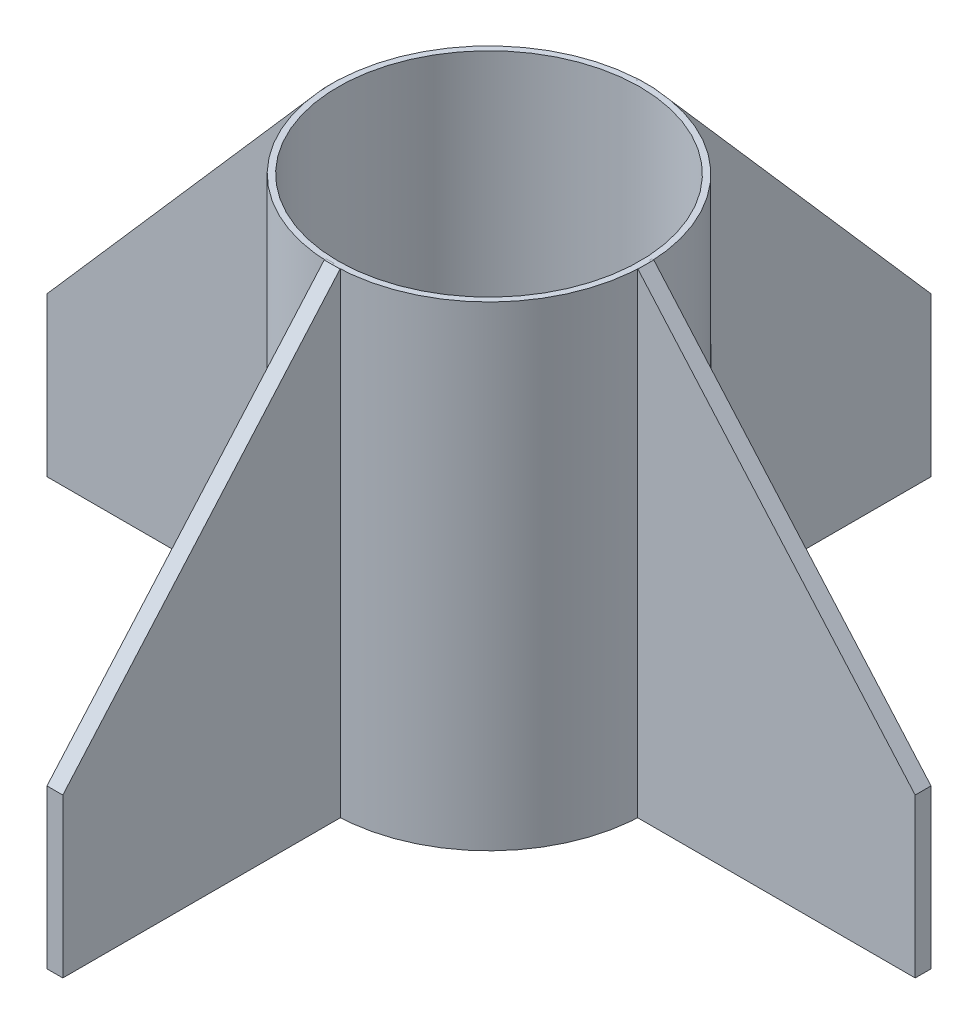
SolidWorks part; units mm, degrees
ref_plane "Front Plane" through (0, 0, 0) normal (0, 0, 1) x (1, 0, 0)
ref_plane "Top Plane" through (0, 0, 0) normal (0, 1, 0) x (1, 0, 0)
ref_plane "Right Plane" through (0, 0, 0) normal (1, 0, 0) x (0, 0, -1)
sketch "Sketch1" plane through (0, 0, 0) normal (0, 1, 0) x (1, 0, 0)
  circle A1 centre (0, 0) radius 38.1
  circle A2 centre (0, 0) radius 39.6
  dimension "D1" = 76.2
  dimension "D2" = 1.5
extrude "Boss-Extrude1" add sketch "Sketch1" along normal blind 120
sketch "Sketch2" plane through (0, 0, 0) normal (0, 0, 1) x (1, 0, 0)
  line L0 (39.6, 0) -> (39.6, 120) construction
  line L1 (39.6, 0) -> (39.6, 120)
  line L2 (39.6, 0) -> (109.6, 0)
  line L3 (109.6, 0) -> (109.6, 40)
  line L4 (109.6, 40) -> (39.6, 120)
  dimension "D1" = 70
  dimension "D2" = 40
extrude "Boss-Extrude2" add sketch "Sketch2" along normal blind 2 and the other way blind 2 separate body
sketch "Sketch3" plane through (39.6, 0, 0) normal (-1, 0, 0) x (0, 0, 1)
  line L0 (-2, 0) -> (2, 0) construction
  line L1 (2, 120) -> (2, 0) construction
  line L2 (-2, 120) -> (2, 120) construction
  line L3 (-2, 120) -> (-2, 0) construction
  line L4 (-2, 0) -> (2, 0)
  line L5 (2, 120) -> (2, 0)
  line L6 (-2, 120) -> (2, 120)
  line L7 (-2, 120) -> (-2, 0)
extrude "Boss-Extrude3" add sketch "Sketch3" along normal blind 0.5
pattern_circular "CirPattern1" count 4 over 360 about axis through (0, 120, 0) along (0, -1, 0) of bodies 103
ref_plane "Launch Rail Plane" through (0, 0, 0) normal (-0.7071, 0, 0.7071) x (0.7071, 0, 0.7071)
sketch "Sketch5" plane through (0, 0, 0) normal (-0.7071, 0, 0.7071) x (0.7071, 0, 0.7071)
  circle A0 centre (0, 60) radius 2
  dimension "D2" = 4
  dimension "D1" = 60
extrude "Cut-Extrude1" cut sketch "Sketch5" against normal up to surface (39.5495 mm away) up to face at (0, 0, 39.6)
